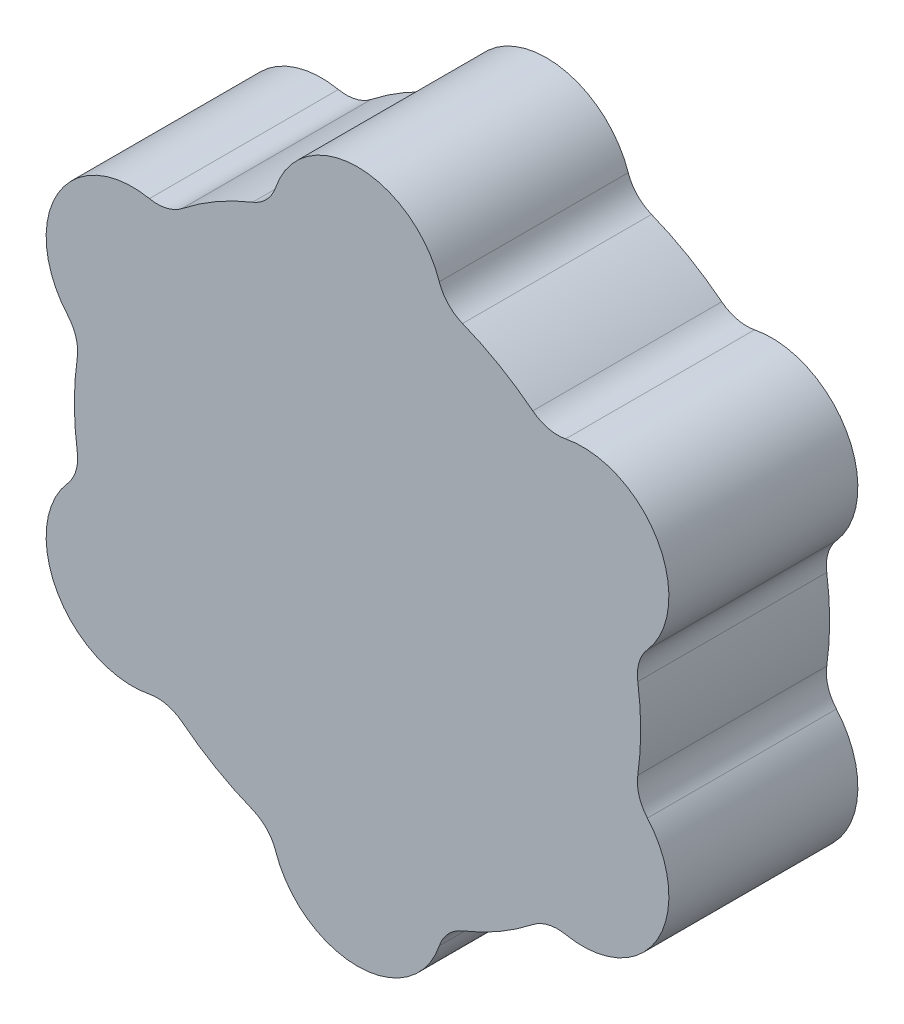
SolidWorks part; units mm, degrees
ref_plane "Front Plane" through (0, 0, 0) normal (0, 0, 1) x (1, 0, 0)
ref_plane "Top Plane" through (0, 0, 0) normal (0, 1, 0) x (1, 0, 0)
ref_plane "Right Plane" through (0, 0, 0) normal (1, 0, 0) x (0, 0, -1)
sketch "Sketch5" plane through (0, 0, 0) normal (0, 0, 1) x (1, 0, 0)
  line L0 (0, 0) -> (0, 13.0969) construction
  circle A0 centre (0, 0) radius 14.2748
  circle A1 centre (0, 0) radius 17.4498 construction
  arc A2 (-4.3232, 13.6044) -> (4.3232, 13.6044) centre (0, 13.0969) cw
  arc A3 (9.6201, 10.5462) -> (13.9434, 3.0582) centre (11.3422, 6.5484) cw
  arc A4 (13.9434, -3.0582) -> (9.6201, -10.5462) centre (11.3422, -6.5484) cw
  arc A5 (4.3232, -13.6044) -> (-4.3232, -13.6044) centre (0, -13.0969) cw
  arc A6 (-9.6201, -10.5462) -> (-13.9434, -3.0582) centre (-11.3422, -6.5484) cw
  arc A7 (-13.9434, 3.0582) -> (-9.6201, 10.5462) centre (-11.3422, 6.5484) cw
  point P7 (0, 0)
  point P8 (0, 0)
  point P24 (0, 0)
  point P25 (0, -13.1064)
  dimension "D1" = 28.5496
  dimension "D2" = 34.8996
  dimension "D3" = 4.3529
  dimension "D4" = 6
extrude "Boss-Extrude2" add sketch "Sketch5" along normal blind 9.525 contours A7 A0 | A2 A0 | A3 A0 | A4 A0 | A5 A0 | A6 A0 | A0 region at (13.3933, 7.7326, 0) region at (13.3933, -7.7326, 0) region at (0, 15.4653, 0) region at (0, -15.4653, 0) region at (-13.3933, 7.7326, 0) region at (-13.3933, -7.7326, 0)
fillet "Fillet1" radius 2.032 12 edges at (-9.6201, 10.5462, 4.7625) (-4.3232, 13.6044, 4.7625) (4.3232, 13.6044, 4.7625) (9.6201, 10.5462, 4.7625) (13.9434, 3.0582, 4.7625) (13.9434, -3.0582, 4.7625) (9.6201, -10.5462, 4.7625) (4.3232, -13.6044, 4.7625) (-4.3232, -13.6044, 4.7625) (-9.6201, -10.5462, 4.7625) (-13.9434, -3.0582, 4.7625) (-13.9434, 3.0582, 4.7625)
